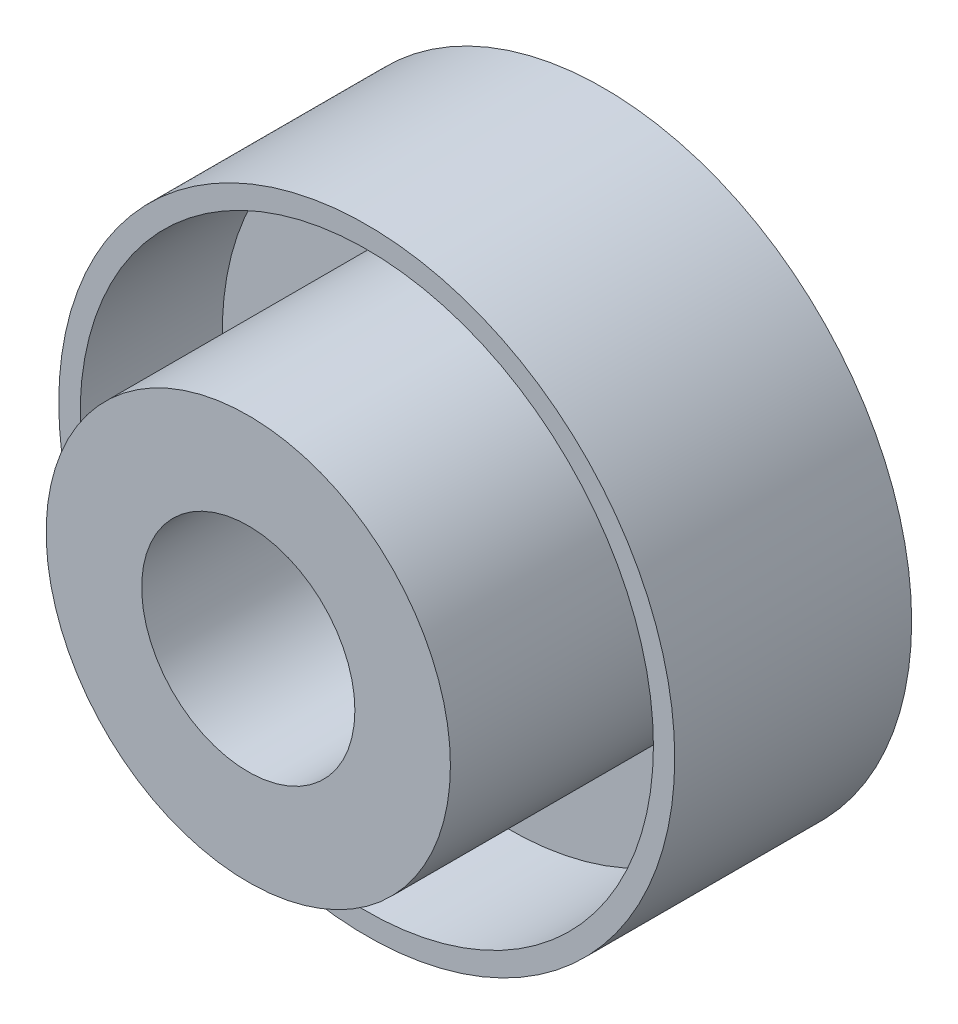
SolidWorks part; units mm, degrees
ref_plane "Спереди" through (0, 0, 0) normal (0, 0, 1) x (1, 0, 0)
ref_plane "Сверху" through (0, 0, 0) normal (0, 1, 0) x (1, 0, 0)
ref_plane "Справа" through (0, 0, 0) normal (1, 0, 0) x (0, 0, -1)
sketch "Эскиз1" plane through (0, 0, 0) normal (0, 0, 1) x (1, 0, 0)
  circle A0 centre (0, 0) radius 13
  circle A1 centre (0, 0) radius 4.5
  circle A2 centre (0, 0) radius 8.5318
  circle A3 centre (0, 0) radius 12.1
extrude "Бобышка-Вытянуть1" add sketch "Эскиз1" along normal blind 4 contours A3 A2 region at (-11.7578, 0, 0)
extrude "Бобышка-Вытянуть2" add sketch "Эскиз1<4>" along normal blind 10 contours A0 A3 region at (-12.6323, 0, 0)
sketch "Эскиз1<4>" plane through (0, 0, 0) normal (0, 0, 1) x (1, 0, 0) same geometry as "Эскиз1"
extrude "Бобышка-Вытянуть3" add sketch "Эскиз1<5>" along normal blind 15 contours A2 A1 region at (-8.2905, 0, 0)
sketch "Эскиз1<5>" plane through (0, 0, 0) normal (0, 0, 1) x (1, 0, 0) same geometry as "Эскиз1"
